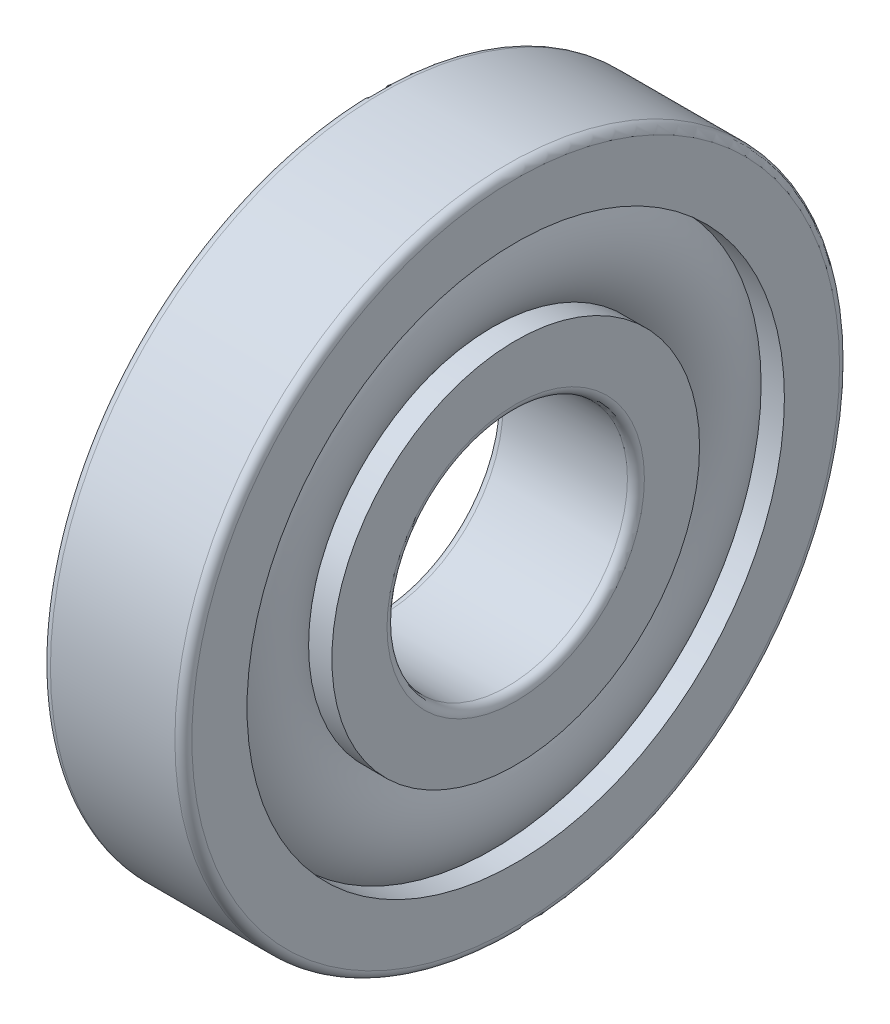
SolidWorks part; units mm, degrees
ref_plane "Plane1" through (0, 0, 0) normal (0, 0, 1) x (1, 0, 0)
ref_plane "Plane2" through (0, 0, 0) normal (0, 1, 0) x (1, 0, 0)
ref_plane "Plane3" through (0, 0, 0) normal (1, 0, 0) x (0, 0, -1)
sketch "Clipboard" plane through (0, 0, 0) normal (0, 0, 1) x (1, 0, 0)
  line L0 (-10, 0) -> (10, 0) construction
  line L1 (0, 0) -> (22.3471, -0.7804)
  line L2 (0, 0) -> (15.9903, 0.5584)
  line L3 (0, 0) -> (22.3471, -0.7804)
  line L4 (0, 0) -> (-22.3573, -0.3902)
  dimension "BallCLRad" = 16
sketch "CagSpiSke" plane through (0, 0, 0) normal (0, 0, 1) x (1, 0, 0)
  line L0 (0.45, 15.25) -> (0.45, 16.75)
  line L1 (0.45, 16.75) -> (-0.45, 16.75)
  line L2 (-0.45, 16.75) -> (-0.45, 15.25)
  line L3 (-0.45, 15.25) -> (0.45, 15.25)
  line L4 (-20.6375, 0) -> (20.6375, 0) construction
  line L5 (0, 0) -> (0, 23.7692) construction
  dimension "OD" = 33.5
  dimension "ID" = 30.5
revolve "CageSpine" add sketch "CagSpiSke" angle 0.001 about L4 reverse direction yes
ref_axis "Axis1" through (-50, 0, 0) along (1, 0, 0)
sketch "CagBalSke" plane through (0, 0, 0) normal (0, 0, 1) x (1, 0, 0)
  line L0 (-4.95, 16) -> (4.95, 16)
  line L1 (-1.905, 16) -> (1.905, 16) construction
  line L2 (-10, 0) -> (10, 0) construction
  line L3 (0, 0) -> (0, 24) construction
  arc A0 (4.95, 16) -> (-4.95, 16) centre (0, 16) cw
  dimension "BallCLRad" = 16
revolve "CageBall" [suppressed] add sketch "CagBalSke" angle 360 about L1 reverse direction yes
pattern_circular "CageBalls" [suppressed] count 2 every 180 about axis through (-50, 0, 0) along (1, 0, 0)
sketch "CagTrmODSke" plane through (0, 0, 0) normal (0, 0, 1) x (1, 0, 0)
  line L0 (4.951, 16.75) -> (4.951, 20.951)
  line L1 (4.951, 20.951) -> (-4.951, 20.951)
  line L2 (-4.951, 20.951) -> (-4.951, 16.75)
  line L3 (-4.951, 16.75) -> (4.951, 16.75)
  line L4 (-20.6375, 0) -> (20.6375, 0) construction
  line L5 (0, 0) -> (0, 25) construction
  dimension "Width" = 9.902
  dimension "ID" = 33.5
  dimension "OD" = 41.902
revolve "CageTrimOD" [suppressed] cut sketch "CagTrmODSke" angle 360 about L4 reverse direction yes
sketch "CagTrmIDSke" plane through (0, 0, 0) normal (0, 0, 1) x (1, 0, 0)
  line L0 (4.951, 11.051) -> (4.951, 15.25)
  line L1 (4.951, 15.25) -> (-4.951, 15.25)
  line L2 (-4.951, 15.25) -> (-4.951, 11.051)
  line L3 (-4.951, 11.051) -> (4.951, 11.051)
  line L4 (-20.6375, 0) -> (20.6375, 0) construction
  line L5 (0, 0) -> (0, 25) construction
  dimension "Width" = 9.902
  dimension "ID" = 22.102
  dimension "OD" = 30.5
revolve "CageTrimID" [suppressed] cut sketch "CagTrmIDSke" angle 360 about L4 reverse direction yes
sketch "BalSimSke" plane through (0, 0, 0) normal (0, 0, 1) x (1, 0, 0)
  line L0 (-10, 0) -> (10, 0) construction
  line L1 (-10, 16) -> (10, 16) construction
  line L2 (0, 0) -> (0, 23) construction
  circle A0 centre (0, 16) radius 4.5
  dimension "BallCLRad" = 16
  dimension "Ball_diameter" = 9
revolve "BallsSimplified" add sketch "BalSimSke" angle 360 about L0
sketch "BalDetSke" plane through (0, 0, 0) normal (0, 0, 1) x (1, 0, 0)
  line L0 (-4.5, 16) -> (4.5, 16)
  line L1 (-1.905, 16) -> (1.905, 16) construction
  line L2 (0, 0) -> (0, 25) construction
  arc A0 (4.5, 16) -> (-4.5, 16) centre (0, 16) cw
  dimension "BallCLRad" = 16
  dimension "Ball_diameter" = 9
revolve "BallDetailed" [suppressed] add sketch "BalDetSke" angle 360 about L1 reverse direction yes
sketch "InnRacSke" plane through (0, 0, 0) normal (0, 0, 1) x (1, 0, 0)
  line L0 (-3.3205, 13) -> (-5, 13)
  line L1 (-5, 13) -> (-5, 9.1)
  line L2 (-4.4, 8.5) -> (4.4, 8.5)
  line L3 (5, 9.1) -> (5, 13)
  line L4 (5, 13) -> (3.3205, 13)
  line L5 (-20.6375, 0) -> (20.6375, 0) construction
  line L6 (0, 0) -> (0, 30) construction
  arc A0 (-5, 9.1) -> (-4.4, 8.5) centre (-4.4, 9.1) ccw
  arc A1 (4.4, 8.5) -> (5, 9.1) centre (4.4, 9.1) ccw
  arc A2 (3.3205, 13) -> (-3.3205, 13) centre (0, 16) cw
  dimension "BallCLRad" = 16
  dimension "Fillet_radius" = 0.6
  dimension "Ball_diameter" = 8.95
  dimension "ID" = 17
  dimension "OD" = 26
  dimension "Width" = 10
revolve "InnerRace" add sketch "InnRacSke" angle 360 about L5 reverse direction yes
sketch "OutRacSke" plane through (0, 0, 0) normal (0, 0, 1) x (1, 0, 0)
  line L0 (-3.3205, 19) -> (-5, 19)
  line L1 (-5, 19) -> (-5, 22.9)
  line L2 (-4.4, 23.5) -> (4.4, 23.5)
  line L3 (5, 22.9) -> (5, 19)
  line L4 (5, 19) -> (3.3205, 19)
  line L5 (-20.6375, 0) -> (20.6375, 0) construction
  line L6 (0, 0) -> (0, 30) construction
  arc A0 (-5, 22.9) -> (-4.4, 23.5) centre (-4.4, 22.9) cw
  arc A1 (4.4, 23.5) -> (5, 22.9) centre (4.4, 22.9) cw
  arc A2 (3.3205, 19) -> (-3.3205, 19) centre (0, 16) ccw
  dimension "BallCLRad" = 16
  dimension "Fillet_radius" = 0.6
  dimension "Ball_diameter" = 8.95
  dimension "Width" = 10
revolve "OuterRace" add sketch "OutRacSke" angle 360 about L5 reverse direction yes
pattern_circular "BallsDetailed" [suppressed] count 2 every 180 about axis through (-50, 0, 0) along (1, 0, 0)
equation "\"BallCLRad@Clipboard\" = ( \"OD@OutRacSke\" + \"ID@InnRacSke\" ) / 4"
equation "\"BallCLRad@BalSimSke\" = \"BallCLRad@Clipboard\""
equation "\"BallCLRad@BalDetSke\" = \"BallCLRad@Clipboard\""
equation "\"BallCLRad@InnRacSke\" = \"BallCLRad@Clipboard\""
equation "\"BallCLRad@OutRacSke\" = \"BallCLRad@Clipboard\""
equation "\"Ball_diameter@InnRacSke\" = \"Ball_diameter@BalDetSke\" - 0.05"
equation "\"Ball_diameter@OutRacSke\" = \"Ball_diameter@BalDetSke\" - 0.05"
equation "\"Ball_diameter@BalSimSke\" = \"Ball_diameter@BalDetSke\""
equation "\"Width@OutRacSke\" = \"Width@InnRacSke\""
equation "\"Fillet_radius@OutRacSke\" = \"Fillet_radius@InnRacSke\""
equation "\"Max_count@Clipboard\" = int( 3.14159265 / atn(( \"Ball_diameter@BalDetSke\" / 2) / sqr( \"BallCLRad@Clipboard\"  *  \"BallCLRad@Clipboard\" - ( \"Ball_diameter@BalDetSke\" / 2) *  ( \"Ball_diameter@BalDetSke\" / 2))))"
equation "\"Max_count@Clipboard\" = ((sgn( \"Max_count@Clipboard\" - \"Count@Clipboard\" )-1)*( \"Max_count@Clipboard\" - \"Count@Clipboard\" ))/-2+ \"Count@Clipboard\""
equation "\"Count@BallsDetailed\" = int( \"Show_count@Clipboard\" ) "
equation "\"Count@BallsDetailed\" = ((sgn( \"Count@BallsDetailed\" - \"Max_count@Clipboard\" )-1)*( \"Count@BallsDetailed\" - \"Max_count@Clipboard\" ))/-2+ \"Max_count@Clipboard\""
equation "\"Count@BallsDetailed\" = ((sgn( \"Count@BallsDetailed\" - \"Min_count@Clipboard\" )+1)*( \"Count@BallsDetailed\" - \"Min_count@Clipboard\"))/2 +\"Min_count@Clipboard\""
equation "\"Angle@BallsDetailed\" = 360.0 / \"Max_count@Clipboard\""
equation "\"BallCLRad@CagBalSke\" = \"BallCLRad@Clipboard\""
equation "\"Count@CageBalls\" = \"Count@BallsDetailed\""
equation "\"Angle@CageBalls\" = \"Angle@BallsDetailed\""
equation "\"Angle@CageSpine\" =  \"Angle@CageBalls\" * ( \"Count@CageBalls\" -1 + int( \"Count@CageBalls\" / \"Max_count@Clipboard\" ) )  + 0.001 -  int( \"Count@CageBalls\" / \"Max_count@Clipboard\" ) * 0.001"
equation "\"Angle@CageSpine\" =  \"Angle@CageSpine\" * int( \"Min_count@Clipboard\" / 2) + int(1 / \"Min_count@Clipboard\")  * 0.001"
equation "\"CageWallOD@CagBalSke\" =  \"Ball_diameter@BalDetSke\" * 1.1"
equation "\"Thickness@CagSpiSke\" =  \"Ball_diameter@BalDetSke\" * 0.1"
equation "\"OD@CagTrmODSke\" = \"BallCLRad@Clipboard\" * 2 + \"CageWallOD@CagBalSke\" + 0.002"
equation "\"ID@CagTrmODSke\" = \"BallCLRad@Clipboard\" * 2 + \"Ball_diameter@BalDetSke\" / 6"
equation "\"OD@CagTrmIDSke\" = \"BallCLRad@Clipboard\" * 2 - \"Ball_diameter@BalDetSke\" / 6"
equation "\"ID@CagTrmIDSke\" = \"BallCLRad@Clipboard\" * 2 - \"CageWallOD@CagBalSke\" + 0.002"
equation "\"OD@CagSpiSke\" = \"ID@CagTrmODSke\""
equation "\"ID@CagSpiSke\" = \"OD@CagTrmIDSke\""
equation "\"Width@CagTrmODSke\" = \"CageWallOD@CagBalSke\" + 0.002"
equation "\"Width@CagTrmIDSke\" = \"CageWallOD@CagBalSke\" + 0.002"
